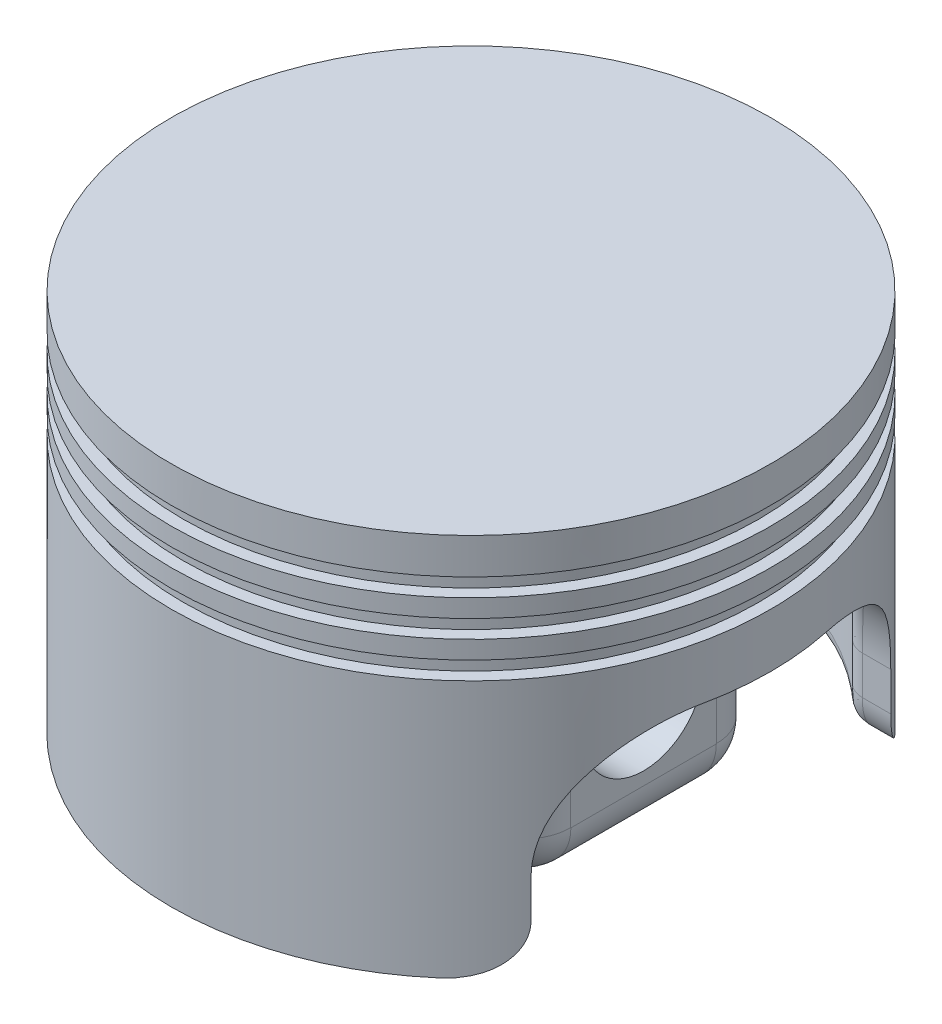
SolidWorks part; units mm, degrees
ref_plane "Front Plane" through (0, 0, 0) normal (0, 0, 1) x (1, 0, 0)
ref_plane "Top Plane" through (0, 0, 0) normal (0, 1, 0) x (1, 0, 0)
ref_plane "Right Plane" through (0, 0, 0) normal (1, 0, 0) x (0, 0, -1)
sketch "Sketch1" plane through (0, 0, 0) normal (0, 0, 1) x (1, 0, 0)
  line L0 (0, 0) -> (63.5, 0)
  line L1 (63.5, 0) -> (63.5, -81.28)
  line L2 (63.5, -81.28) -> (57.15, -81.28)
  line L3 (57.15, -81.28) -> (57.15, -19)
  line L4 (57.15, -19) -> (0, -19)
  line L5 (0, -19) -> (0, 0)
  dimension "D1" = 63.5
  dimension "D2" = 81.28
  dimension "D3" = 6.35
  dimension "D4" = 19
revolve "Revolve1" add sketch "Sketch1" angle 360 about L5
sketch "Sketch2" plane through (0, 0, 0) normal (0, 0, 1) x (1, 0, 0)
  line L0 (60.96, -7.62) -> (60.96, -11.43)
  line L1 (60.96, -11.43) -> (63.5, -11.43)
  line L2 (63.5, -11.43) -> (63.5, -7.62)
  line L3 (63.5, -7.62) -> (60.96, -7.62)
  line L4 (63.5, 0) -> (-63.5, 0) construction
  dimension "D1" = 7.62
  dimension "D2" = 2.54
  dimension "D3" = 3.81
  dimension "D4" = 63.5
ref_axis "Axis2" through (0, 0, 0) along (0, -1, 0)
revolve "Cut-Revolve1" cut sketch "Sketch2" angle 360 about axis through (0, 0, 0) along (0, -1, 0)
pattern_linear "LPattern1" count 3 spacing 7.62 along (0, -1, 0) of "Cut-Revolve1"
sketch "Sketch3" plane through (0, 0, 0) normal (1, 0, 0) x (0, 0, -1)
  line L0 (0, 0) -> (0, -81.28) construction
  line L1 (-38.1, -38.1) -> (38.1, -38.1)
  line L2 (-38.1, -38.1) -> (-38.1, -81.28)
  line L3 (-38.1, -81.28) -> (38.1, -81.28)
  line L4 (38.1, -38.1) -> (38.1, -81.28)
  line L5 (-38.1, -38.1) -> (38.1, -81.28) construction
  line L6 (-38.1, -81.28) -> (38.1, -38.1) construction
  line L7 (-57.15, -81.28) -> (57.15, -81.28) construction
  line L8 (63.5, 0) -> (-63.5, 0) construction
  point P0 (0, -59.69)
  dimension "D1" = 76.2
  dimension "D2" = 38.1
extrude "Cut-Extrude1" cut sketch "Sketch3" against normal mid plane 220
fillet "Fillet1" radius 25 4 edges at (-46.6985, -38.1, -38.1) (-46.6985, -38.1, 38.1) (46.6985, -38.1, -38.1) (46.6985, -38.1, 38.1)
fillet "Fillet2" radius 10 4 edges at (-46.6985, -81.28, -38.1) (46.6985, -81.28, -38.1) (-46.6985, -81.28, 38.1) (46.6985, -81.28, 38.1)
sketch "Sketch4" plane through (0, -19, 0) normal (0, -1, 0) x (1, 0, 0)
  line L1 (-36.55, -25.4) -> (-17.55, -25.4)
  line L2 (-36.55, -25.4) -> (-36.55, 25.4)
  line L3 (-36.55, 25.4) -> (-17.55, 25.4)
  line L4 (-17.55, -25.4) -> (-17.55, 25.4)
  line L5 (-36.55, -25.4) -> (-17.55, 25.4) construction
  line L6 (-36.55, 25.4) -> (-17.55, -25.4) construction
  point P0 (-27.05, 0)
  dimension "D1" = 19
  dimension "D2" = 50.8
  dimension "D3" = 17.55
extrude "Boss-Extrude1" add sketch "Sketch4" along normal blind 63.5
mirror "Mirror1" about plane through (0, 0, 0) normal (1, 0, 0) of "Boss-Extrude1"
fillet "Fillet3" radius 10 4 edges at (27.05, -82.5, 25.4) (27.05, -82.5, -25.4) (-27.05, -82.5, -25.4) (-27.05, -82.5, 25.4)
fillet "Fillet4" radius 10 10 edges at (-36.55, -45.75, 25.4) (-36.55, -79.5711, 22.4711) (-36.55, -45.75, -25.4) (-36.55, -79.5711, -22.4711) (-36.55, -82.5, 0) (17.55, -45.75, -25.4) (17.55, -79.5711, -22.4711) (17.55, -45.75, 25.4) (17.55, -79.5711, 22.4711) (17.55, -82.5, 0)
fillet "Fillet5" radius 10 10 edges at (36.55, -45.75, 25.4) (36.55, -79.5711, 22.4711) (36.55, -45.75, -25.4) (36.55, -79.5711, -22.4711) (36.55, -82.5, 0) (-17.55, -45.75, -25.4) (-17.55, -79.5711, -22.4711) (-17.55, -45.75, 25.4) (-17.55, -79.5711, 22.4711) (-17.55, -82.5, 0)
sketch "Sketch5" plane through (-36.55, 0, 0) normal (-1, 0, 0) x (0, 0, 1)
  line L0 (0, 0) -> (0, -81.28) construction
  line L1 (15.4, -82.5) -> (-15.4, -82.5) construction
  circle A0 centre (0, -57.1) radius 12.7
  dimension "D1" = 25.4
  dimension "D2" = 25.4
extrude "Cut-Extrude2" cut sketch "Sketch5" against normal blind 130.5
fillet "Fillet6" radius 5 17 edges at (-41.3657, -76.2692, -39.4335) (-42.5971, -67.19, -38.1) (-49.5699, -43.3611, -28.4419) (-57.15, -38.1, 0) (-45.69, -49.8982, 34.33) (-42.5971, -67.19, 38.1) (-40.0022, -78.1316, 40.816) (0, -81.28, 57.15) (41.3657, -76.2692, 39.4335) (42.5971, -67.19, 38.1) (49.5699, -43.3611, 28.4419) (57.15, -38.1, 0) (45.69, -49.8982, -34.33) (42.5971, -67.19, -38.1) (40.0022, -78.1316, -40.816) (0, -19, -57.15) (0, -81.28, -57.15)
